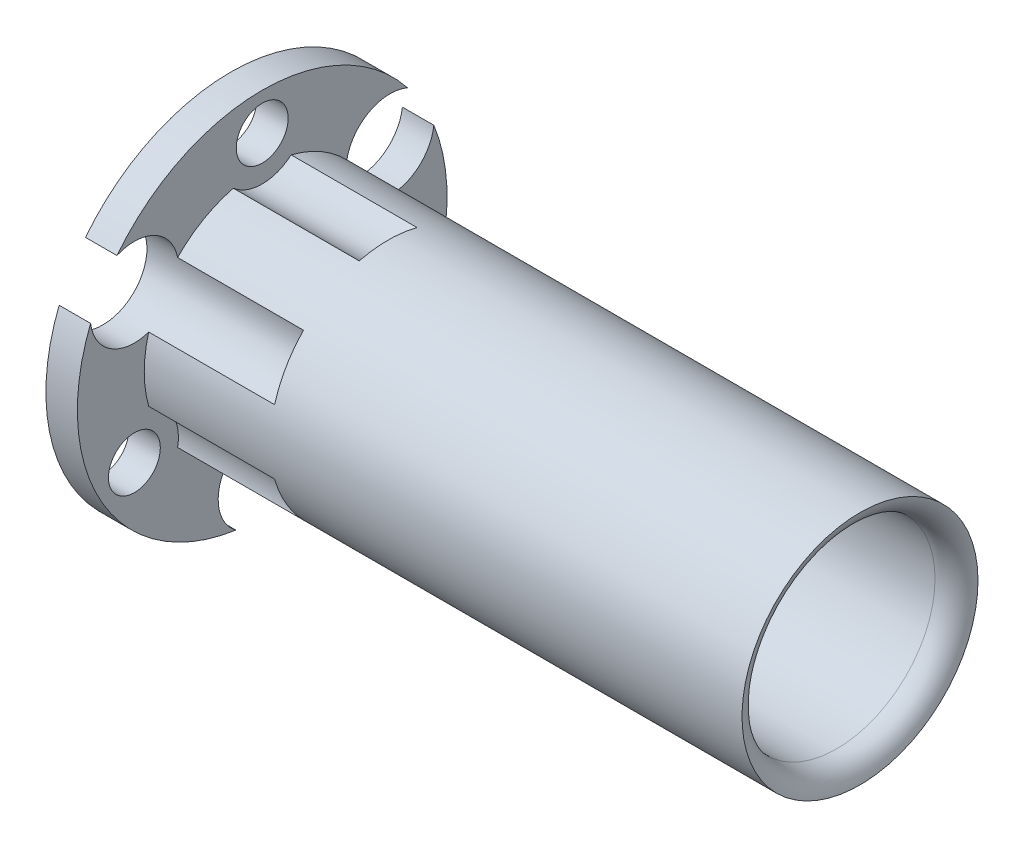
SolidWorks part; units mm, degrees
ref_plane "Front Plane" through (0, 0, 0) normal (0, 0, 1) x (1, 0, 0)
ref_plane "Top Plane" through (0, 0, 0) normal (0, 1, 0) x (1, 0, 0)
ref_plane "Right Plane" through (0, 0, 0) normal (1, 0, 0) x (0, 0, -1)
sketch "Sketch1" plane through (0, 0, 0) normal (1, 0, 0) x (0, 0, -1)
  line L0 (0, 9.385) -> (0, 0) construction
  line L1 (0, 0) -> (0, -9.385) construction
  circle A0 centre (0, 0) radius 6.25
  circle A1 centre (0, 0) radius 11.75
  circle A2 centre (0, 9.385) radius 1.65
  circle A3 centre (8.1276, -4.6925) radius 1.65
  circle A4 centre (-8.1276, -4.6925) radius 1.65
  circle A8 centre (0, 0) radius 7.5
  circle A9 centre (0, -9.385) radius 2.8
  circle A10 centre (-8.1276, -4.6925) radius 2.8
  circle A11 centre (-8.1276, 4.6925) radius 2.8
  circle A12 centre (0, 9.385) radius 2.8
  circle A13 centre (8.1276, 4.6925) radius 2.8
  circle A14 centre (8.1276, -4.6925) radius 2.8
  point P18 (0, 0)
  point P19 (0, 0)
  dimension "D2" = 3.3
  dimension "D3" = 23.5
  dimension "D4" = 12.5
  dimension "D6" = 1.25
  dimension "D8" = 6
  dimension "D7" = 5.6
  dimension "D1" = 9.385
  dimension "D5" = 3
extrude "Boss-Extrude1" add sketch "Sketch1" along normal blind 2 contours A11 A1 A10 A8 | A14 A8 A13 A12 A11 A10 A9 A0 | A12 A1 A11 A8 | A13 A1 A12 A8 | A14 A1 A13 A8 | A14 A8 A9 A1 | A10 A1 A9 A8 | A8 A10 | A8 A9 | A8 A14 | A8 A13 | A8 A12 | A8 A11 | A1 A14 A8 A3 | A8 A10 A1 A4 | A1 A12 A8 A2 region at (0, 0, -9.8051) region at (0, -5.8357, -10.1076) region at (0, 8.4915, -4.9025) region at (0, 3.5422, -6.1352) region at (0, 1.0036, -7.2217) region at (0, -8.4915, -4.9025) region at (0, -3.5422, -6.1352) region at (0, 10.609, -2.4383) region at (0, 8.4915, 4.9025) region at (0, 7.0844, 0) region at (0, -8.4915, 4.9025) region at (0, -7.0844, 0) region at (0, -5.8357, 10.1076) region at (0, 0, 9.8051) region at (0, 3.5422, 6.1352) region at (0, -3.5422, 6.1352)
extrude "Boss-Extrude2" add sketch "Sketch1<3>" along normal blind 40 contours A8 A0 | A8 A11 | A8 A10 | A8 A9 | A8 A14 | A8 A13 | A8 A12 region at (0, 3.5422, -6.1352) region at (0, 1.0036, -7.2217) region at (0, -3.5422, -6.1352) region at (0, 7.0844, 0) region at (0, -7.0844, 0) region at (0, 3.5422, 6.1352) region at (0, -3.5422, 6.1352)
sketch "Sketch1<3>" plane through (0, 0, 0) normal (1, 0, 0) x (0, 0, -1) same geometry as "Sketch1"
extrude "Cut-Extrude2" cut sketch "Sketch1<4>" along normal blind 8 from surface contours A8 A9 A1 | A8 A9 | A8 A10 | A8 A14 | A8 A13 | A8 A12 | A8 A11 region at (0, 3.5422, -6.1352) region at (0, -3.5422, -6.1352) region at (0, -9.5142, 0) region at (0, 7.0844, 0) region at (0, -7.0844, 0) region at (0, 3.5422, 6.1352) region at (0, -3.5422, 6.1352) starting at face at (2, -4.6925, -9.7776)
sketch "Sketch1<4>" plane through (0, 0, 0) normal (1, 0, 0) x (0, 0, -1) same geometry as "Sketch1"
extrude "Cut-Extrude3" cut sketch "Sketch1<5>" against normal through all from surface contours A8 A9 | A8 A13 | A8 A11 region at (0, 3.5422, -6.1352) region at (0, -7.0844, 0) region at (0, 3.5422, 6.1352) starting at face at (2, 3.5213, 6.099)
sketch "Sketch1<5>" plane through (0, 0, 0) normal (1, 0, 0) x (0, 0, -1) same geometry as "Sketch1"
fillet "Fillet1" radius 1.5 1 edges at (40, 0, -6.25)
